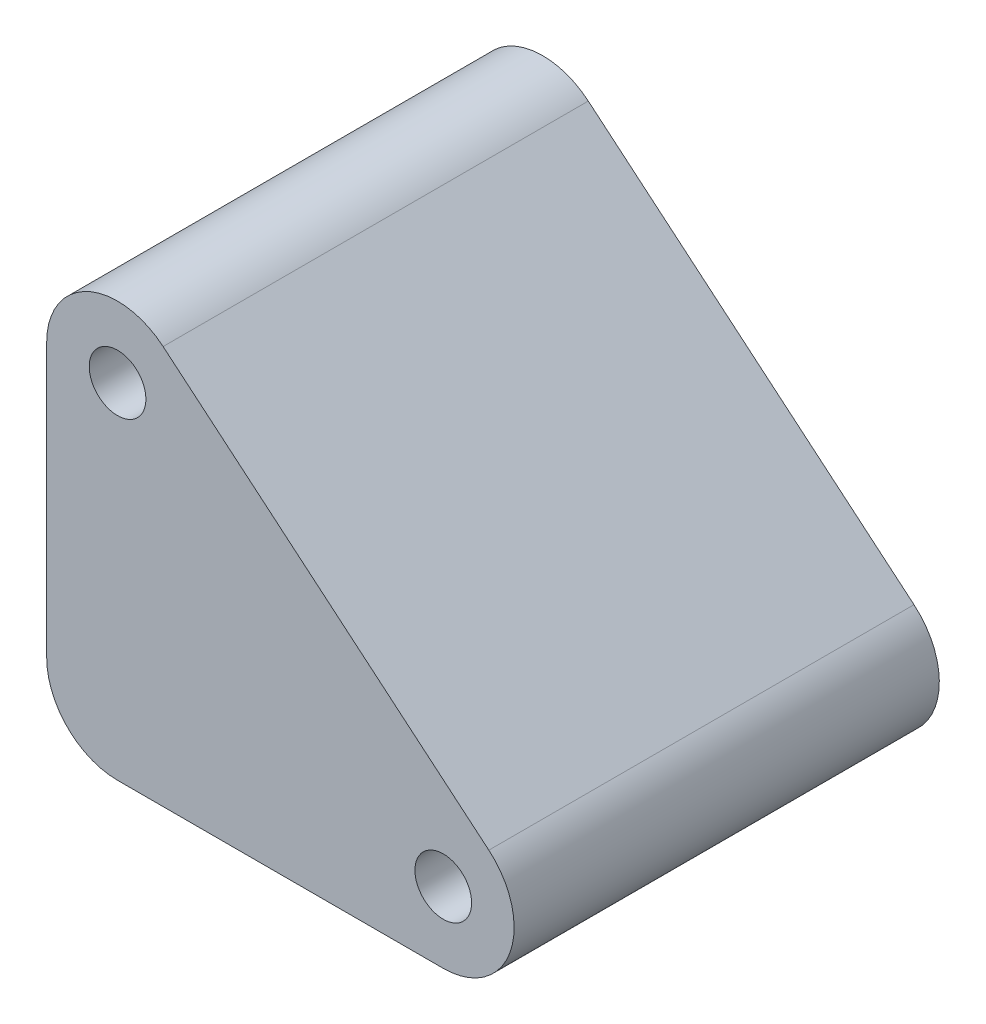
SolidWorks part; units mm, degrees
ref_plane "Front Plane" through (0, 0, 0) normal (0, 0, 1) x (1, 0, 0)
ref_plane "Top Plane" through (0, 0, 0) normal (0, 1, 0) x (1, 0, 0)
ref_plane "Right Plane" through (0, 0, 0) normal (1, 0, 0) x (0, 0, -1)
sketch "Sketch1" plane through (0, 0, 0) normal (0, 0, 1) x (1, 0, 0)
  line L0 (-246.5743, 135.3883) -> (-223.593, 116.1047)
  line L1 (-226.8069, 107.2745) -> (-249.7883, 107.2745)
  line L2 (-254.7883, 112.2745) -> (-254.7883, 131.5581)
  circle A0 centre (-226.8069, 112.2745) radius 2 construction
  circle A1 centre (-249.7883, 131.5581) radius 2 construction
  circle A2 centre (-226.8069, 112.2745) radius 2
  circle A3 centre (-249.7883, 131.5581) radius 2
  arc A4 (-223.593, 116.1047) -> (-226.8069, 107.2745) centre (-226.8069, 112.2745) cw
  arc A5 (-249.7883, 107.2745) -> (-254.7883, 112.2745) centre (-249.7883, 112.2745) cw
  arc A6 (-254.7883, 131.5581) -> (-246.5743, 135.3883) centre (-249.7883, 131.5581) cw
  dimension "D1" = 5
  dimension "D2" = 5
  dimension "D3" = 5
  dimension "D4" = 19.2836
  dimension "D5" = 22.9813
extrude "Boss-Extrude1" add sketch "Sketch1" along normal blind 15 and the other way blind 15
